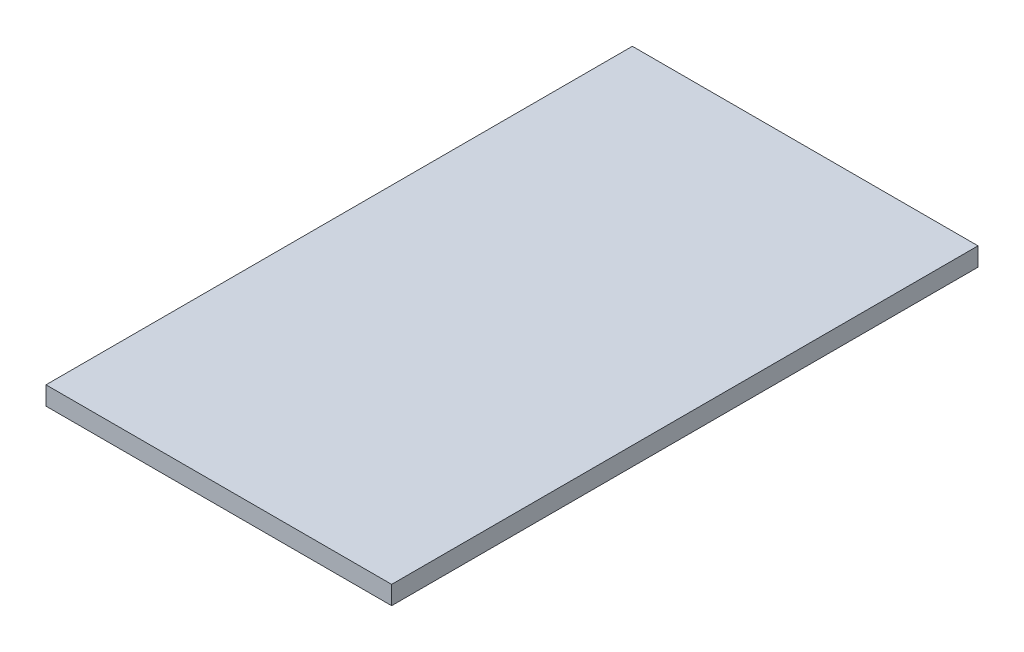
SolidWorks part; units mm, degrees
material "Perspex (TM) GS Acrylic Cast Sheet"
ref_plane "Front Plane" through (0, 0, 0) normal (0, 0, 1) x (1, 0, 0)
ref_plane "Top Plane" through (0, 0, 0) normal (0, 1, 0) x (1, 0, 0)
ref_plane "Right Plane" through (0, 0, 0) normal (1, 0, 0) x (0, 0, -1)
sketch "Sketch1" plane through (0, 0, 0) normal (0, 1, 0) x (1, 0, 0)
  line L1 (-84, -142.5) -> (84, -142.5)
  line L2 (-84, -142.5) -> (-84, 142.5)
  line L3 (-84, 142.5) -> (84, 142.5)
  line L4 (84, -142.5) -> (84, 142.5)
  line L5 (-84, -142.5) -> (84, 142.5) construction
  line L6 (-84, 142.5) -> (84, -142.5) construction
  point P0 (0, 0)
  dimension "D2" = 285
  dimension "D1" = 168
extrude "Boss-Extrude1" add sketch "Sketch1" along normal blind 9
equation "\"PCLength\"= 150mm'Length across I/O from PS to GPU"
equation "\"PCWidth\"= 340mm'Distance of longest part parallel to GPU(ussually GPU)"
equation "\"PCHeight\"= 190mm'Tallest point with mobo laying flat"
equation "\"WallThickness\"= 9mm'Thickness of each outer tank wall"
equation "\"ThermoBarrierThickness\"= 6mm'Thickness of barrier between hot side and cold side"
equation "\"HotSideGap\"= 15mm'Space in the hot side that hot fluid flows into"
equation "\"PCClearance\"= 40mm'Clearance from top of tank to top of PC"
equation "\"RadiatorHeight\"= 277.37mm'Final Height from ground of radiators"
equation "\"D2@Sketch1\"=\"PCHeight\" + \"ThermoBarrierThickness\" + \"HotSideGap\" + (2 * \"WallThickness\") + \"AirflowGap\" + 30"
equation "\"D1@Boss-Extrude1\"=\"WallThickness\""
equation "\"D1@Sketch1\"=\"PCLength\" + (2 * \"WallThickness\")"
equation "\"AirflowGap\"= 26mm'Distance between radiators and tank for airflow"
equation "\"VolumeSubtraction\"= 230mm"
